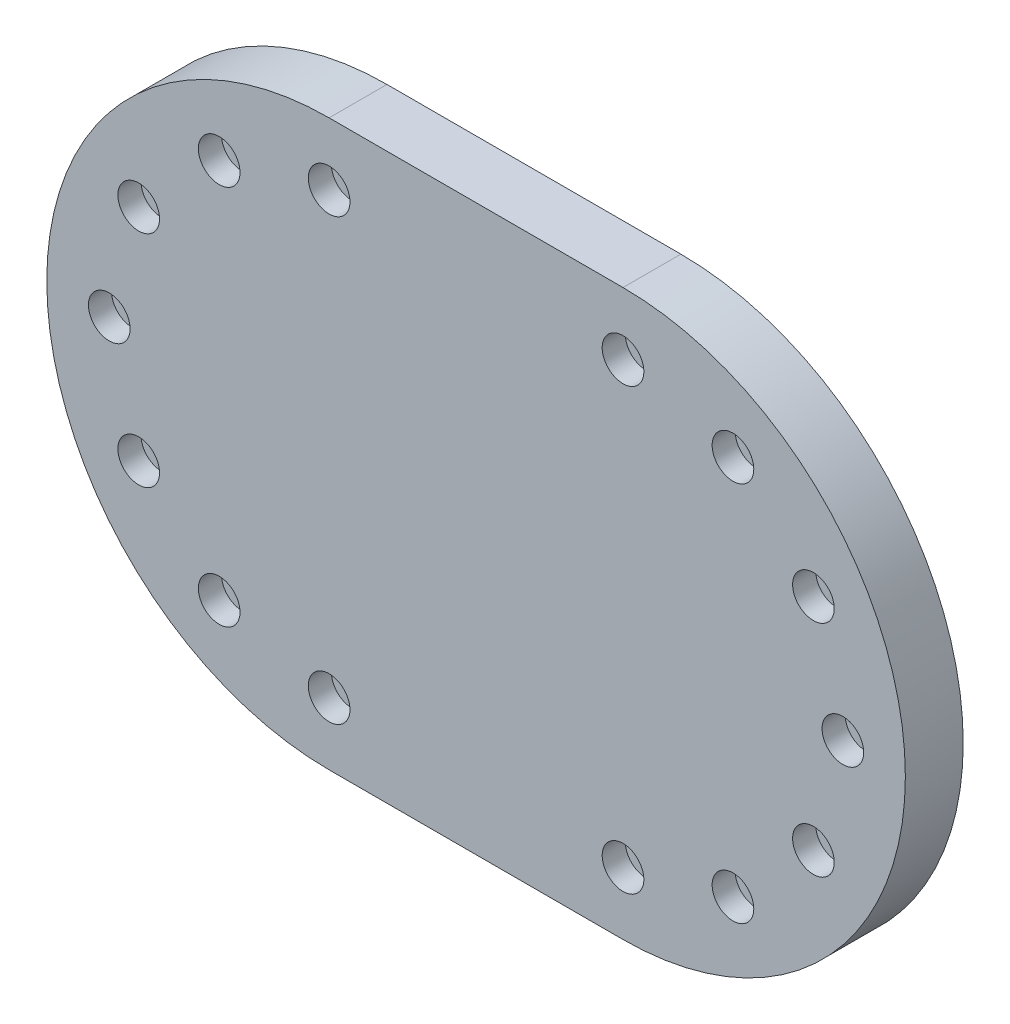
SolidWorks part; units mm, degrees
ref_plane "Plano frontal" through (0, 0, 0) normal (0, 0, 1) x (1, 0, 0)
ref_plane "Plano superior" through (0, 0, 0) normal (0, 1, 0) x (1, 0, 0)
ref_plane "Plano direito" through (0, 0, 0) normal (1, 0, 0) x (0, 0, -1)
sketch "Esboço1" plane through (0, 0, 0) normal (0, 0, 1) x (1, 0, 0)
  line L0 (-31.75, 0) -> (31.75, 0) construction
  line L1 (-31.75, 61) -> (31.75, 61)
  line L2 (-31.75, -61) -> (31.75, -61)
  line L3 (-31.75, 0) -> (31.75, 0) construction
  line L4 (-31.75, 11.5) -> (31.75, 11.5)
  line L5 (-31.75, -11.5) -> (31.75, -11.5)
  arc A0 (-31.75, 61) -> (-31.75, -61) centre (-31.75, 0) ccw
  arc A1 (31.75, -61) -> (31.75, 61) centre (31.75, 0) ccw
  arc A3 (-31.75, 11.5) -> (-31.75, -11.5) centre (-31.75, 0) ccw
  arc A4 (31.75, -11.5) -> (31.75, 11.5) centre (31.75, 0) ccw
  point P2 (0, 0)
  point P10 (0, 0)
  dimension "D2" = 63.5
  dimension "D3" = 11.5
  dimension "D1" = 122
extrude "Ressalto-extrusão4" add sketch "Esboço1" along normal blind 12.5 contours L5 A4 L4 A3 | L2 A1 L1 A0 A4 L5 A3 L4 region at (0, 58.7798, 0) region at (0, 0, 0)
extrude "Corte-extrusão2" cut sketch "Esboço1<7>" along normal blind 6.25 contours L5 A4 L4 A3 region at (0, 0, 0)
sketch "Esboço1<7>" plane through (0, 0, 0) normal (0, 0, 1) x (1, 0, 0) same geometry as "Esboço1"
hole_wizard "Furo5" positions "Esboço14" profile "Esboço15" legacy end condition through all
sketch "Esboço14" plane through (0, 0, 12.5) normal (0, 0, 1) x (1, 0, 0)
  point P0 (-31.75, 47.5)
  point P4 (0, 0)
  dimension "D1" = 47.5
sketch "Esboço15" plane through (-31.75, 47.5, 12.5) normal (1, 0, 0) x (0, -1, 0)
  line L0 (0, 0) -> (0, 12.5)
  line L1 (0, 12.5) -> (2.5, 12.5)
  line L2 (2.5, 12.5) -> (2.5, 5)
  line L3 (2.5, 5) -> (4.5, 5)
  line L4 (4.5, 5) -> (4.5, 0)
  line L5 (4.5, 0) -> (0, 0)
  line L6 (0, 110) -> (0, -10) construction
  dimension "Diameter" = 5
  dimension "Depth" = 12.5
  dimension "C-Bore Diameter" = 9
  dimension "C-Bore Depth" = 5
pattern_circular "PadrãoCircular3" count 7 over 180 about axis through (-31.75, 0, 12.5) along (0, 0, -1) of "Furo5" reverse direction yes
hole_wizard "Furo6" positions "Esboço16" profile "Esboço17" legacy end condition through all
sketch "Esboço16" plane through (0, 0, 12.5) normal (0, 0, 1) x (1, 0, 0)
  point P0 (31.75, 47.5)
  dimension "D1" = 47.5
sketch "Esboço17" plane through (31.75, 47.5, 12.5) normal (1, 0, 0) x (0, -1, 0)
  line L0 (0, 0) -> (0, 12.5)
  line L1 (0, 12.5) -> (2.5, 12.5)
  line L2 (2.5, 12.5) -> (2.5, 5)
  line L3 (2.5, 5) -> (4.5, 5)
  line L4 (4.5, 5) -> (4.5, 0)
  line L5 (4.5, 0) -> (0, 0)
  line L6 (0, 110) -> (0, -10) construction
  dimension "Diameter" = 5
  dimension "Depth" = 12.5
  dimension "C-Bore Diameter" = 9
  dimension "C-Bore Depth" = 5
pattern_circular "PadrãoCircular4" count 7 over 180 about axis through (31.75, 0, 12.5) along (0, 0, -1) of "Furo6"
